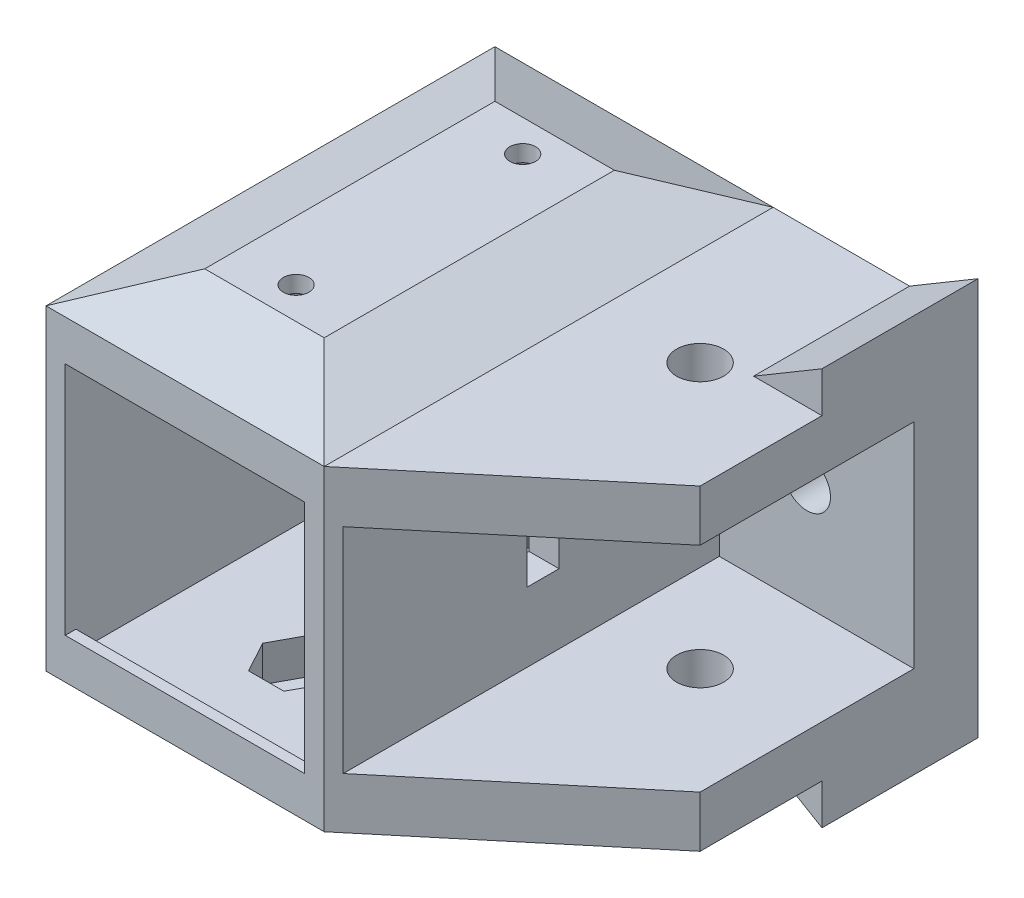
SolidWorks part; units mm, degrees
material "ABS"
ref_plane "Front Plane" through (0, 0, 0) normal (0, 0, 1) x (1, 0, 0)
ref_plane "Top Plane" through (0, 0, 0) normal (0, 1, 0) x (1, 0, 0)
ref_plane "Right Plane" through (0, 0, 0) normal (1, 0, 0) x (0, 0, -1)
sketch "Sketch1" plane through (0, 0, 0) normal (0, 0, 1) x (1, 0, 0)
  line L1 (2, 0) -> (45.2, 0)
  line L2 (0, 2) -> (0, 27.6)
  line L3 (2, 29.6) -> (45.2, 29.6)
  line L4 (45.2, 0) -> (45.2, 29.6)
  line L5 (2, 0) -> (0, 0)
  line L6 (-1.4495, 14.8) -> (46.6426, 14.8) construction
  line L7 (0, 0) -> (0, 2)
  line L8 (1.8, 27.7) -> (24.2, 27.7)
  line L9 (1.8, 27.7) -> (1.8, 1.9)
  line L10 (1.8, 1.9) -> (24.2, 1.9)
  line L11 (24.2, 27.7) -> (24.2, 1.9)
  line L12 (2, 29.6) -> (0, 29.6)
  line L13 (0, 29.6) -> (0, 27.6)
  circle A0 centre (35.2, 14.8) radius 2.2
  dimension "D10" = 10
  dimension "D2" = 11
  dimension "D3" = 14.8
  dimension "D4" = 1.8
  dimension "D7" = 22.4
  dimension "D8" = 25.8
  dimension "D9" = 1.9
extrude "Boss-Extrude1" add sketch "Sketch1" along normal blind 42
sketch "Sketch2" plane through (0, 29.6, 0) normal (0, 1, 0) x (1, 0, 0)
  line L0 (45.2, -26) -> (26.03, -42)
  line L1 (45.2, -42) -> (45.2, 0) construction
  line L2 (45.2, -42) -> (0, -42) construction
  line L3 (26.03, -42) -> (45.2, -42)
  line L4 (45.2, -42) -> (45.2, -26)
  dimension "D1" = 19.17
  dimension "D2" = 16
extrude "Cut-Extrude1" cut sketch "Sketch2" against normal through all
sketch "Sketch3" plane through (0, 0, 0) normal (0, 0, -1) x (-1, 0, 0)
  line L0 (-38.8, 0) -> (-45.2, -3.8)
  line L1 (0, 0) -> (-45.2, 0) construction
  line L2 (-45.2, -3.8) -> (-45.2, 0)
  line L3 (-45.2, 0) -> (-38.8, 0)
  line L4 (-46.2203, 14.8) -> (1.3358, 14.8) construction
  line L5 (-45.2, 29.6) -> (-38.8, 29.6)
  line L6 (-45.2, 33.4) -> (-45.2, 29.6)
  line L7 (-38.8, 29.6) -> (-45.2, 33.4)
  dimension "D1" = 6.4
  dimension "D2" = 3.8
extrude "Boss-Extrude2" add sketch "Sketch3" against normal blind 14.6
sketch "Sketch4" plane through (45.2, 0, 0) normal (1, 0, 0) x (0, 0, -1)
  line L0 (-42, 0) -> (-42, 29.6) construction
  line L1 (-6, 24.8) -> (-42, 24.8)
  line L2 (-6, 24.8) -> (-6, 4.8)
  line L3 (-6, 4.8) -> (-42, 4.8)
  line L4 (-42, 24.8) -> (-42, 4.8)
  line L5 (-26, 29.6) -> (-14.6, 29.6) construction
  line L6 (-26, 0) -> (-14.6, 0) construction
  line L7 (0, -3.8) -> (0, 33.4) construction
  dimension "D1" = 4.8
  dimension "D2" = 4.8
  dimension "D3" = 6
extrude "Cut-Extrude2" cut sketch "Sketch4" against normal blind 18.2
sketch "Sketch5" plane through (0, 29.6, 0) normal (0, 1, 0) x (1, 0, 0)
  line L0 (45.2, -26) -> (45.2, -14.6) construction
  line L1 (38.8, 0) -> (0, 0) construction
  circle A0 centre (35.2, -16) radius 2.2
  dimension "D1" = 10
  dimension "D2" = 16
extrude "Cut-Extrude3" cut sketch "Sketch5" against normal through all
sketch "Sketch16" plane through (0, 29.6, 0) normal (0, 1, 0) x (1, 0, 0)
  line L0 (26.03, -42) -> (26.03, 0)
  line L2 (26.03, 0) -> (0, 0)
  line L3 (0, 0) -> (0, -42)
  line L4 (0, -42) -> (26.03, -42)
  line L8 (0, -42) -> (0, 0) construction
extrude "Boss-Extrude6" add sketch "Sketch16" along normal blind 3
chamfer "Chamfer1" distance 3 angle 68 4 edges at (13.015, 32.6, 42) (26.03, 32.6, 21) (13.015, 32.6, 0) (0, 32.6, 21)
ref_plane "Plane1" through (0, 14.8, 0) normal (0, -1, 0) x (-1, 0, 0)
mirror "Mirror7" about plane through (0, 14.8, 0) normal (0, -1, 0) of "Boss-Extrude6", "Chamfer1"
sketch "Sketch6" plane through (0, 29.6, 0) normal (0, 1, 0) x (1, 0, 0)
  line L0 (11.35, -13.4) -> (9.7752, -10.5)
  line L1 (11.35, -13.4) -> (14.65, -13.4)
  line L3 (14.65, -13.4) -> (16.2442, -10.5)
  line L4 (14.65, -7.6) -> (16.2442, -10.5)
  line L5 (38.8, 0) -> (26.03, 0) construction
  line L6 (13, -2.324) -> (13, -15.7052) construction
  line L7 (11.35, -7.6) -> (9.7752, -10.5)
  line L8 (1.8, -42) -> (1.8, 0) construction
  line L9 (11.35, -7.6) -> (14.65, -7.6)
  line L13 (16.2442, -10.5) -> (9.7752, -10.5) construction
  dimension "D2" = 3.3
  dimension "D3" = 1.65
  dimension "D4" = 10.5
  dimension "D5" = 11.2
  dimension "D6" = 6.469
  dimension "D7" = 1.5942
  dimension "D11" = 2.9
extrude "Cut-Extrude4" cut sketch "Sketch6" along normal blind 3.35 from surface at -1.9 contours L7 L0 L1 L3 L4 L9 starting at face at (13, 27.7, 21)
sketch "Sketch10" plane through (0, 32.6, 0) normal (0, 1, 0) x (1, 0, 0)
  line L3 (13, -2.324) -> (13, -15.7052) construction
  line L4 (11.35, -7.6) -> (14.65, -7.6) construction
  circle A0 centre (13, -10.4) radius 1.2
  dimension "D1" = 2.8
extrude "Cut-Extrude10" cut sketch "Sketch10" against normal through all contours A0
mirror "Mirror4" about plane through (0, 14.8, 0) normal (0, -1, 0) of "Cut-Extrude4"
sketch "Sketch13" plane through (0, 0, 42) normal (0, 0, 1) x (1, 0, 0)
  line L0 (24.2, 1.9) -> (24.2, 27.7) construction
  line L1 (1.8, 1.9) -> (24.2, 1.9)
  line L2 (1.8, 1.9) -> (1.8, 3.8)
  line L3 (1.8, 3.8) -> (24.2, 3.8)
  line L4 (24.2, 1.9) -> (24.2, 3.8)
  line L6 (1.8, 27.7) -> (24.2, 27.7)
  line L7 (1.8, 27.7) -> (1.8, 25.8)
  line L8 (1.8, 25.8) -> (24.2, 25.8)
  line L9 (24.2, 27.7) -> (24.2, 25.8)
  dimension "D1" = 1.9
  dimension "D2" = 1.9
extrude "Boss-Extrude4" add sketch "Sketch13" against normal blind 1
sketch "Sketch14" plane through (27, 0, 0) normal (1, 0, 0) x (0, 0, -1)
  line L0 (-6, 24.8) -> (-41.1904, 24.8) construction
  line L1 (-8, 18.3) -> (-11, 18.3)
  line L2 (-8, 18.3) -> (-8, 11.3)
  line L3 (-8, 11.3) -> (-11, 11.3)
  line L4 (-11, 18.3) -> (-11, 11.3)
  line L5 (-21, 18.3) -> (-24, 18.3)
  line L6 (-21, 18.3) -> (-21, 11.3)
  line L7 (-21, 11.3) -> (-24, 11.3)
  line L8 (-24, 18.3) -> (-24, 11.3)
  line L9 (-42, 24.8) -> (-42, 4.8) construction
  dimension "D1" = 6.5
  dimension "D2" = 6.5
  dimension "D3" = 7
  dimension "D4" = 7
  dimension "D5" = 18
  dimension "D6" = 3
  dimension "D7" = 10
  dimension "D8" = 3
extrude "Cut-Extrude11" cut sketch "Sketch14" against normal up to surface (2.8 mm away) up to face at (24.2, 14.8, 31)
sketch "Sketch15" plane through (0, 0, 0) normal (0, 0, -1) x (-1, 0, 0)
  line L1 (-1.8, 1.9) -> (-24.2, 1.9)
  line L2 (-1.8, 1.9) -> (-1.8, 3.8)
  line L3 (-1.8, 3.8) -> (-24.2, 3.8)
  line L4 (-24.2, 1.9) -> (-24.2, 3.8)
  line L5 (-1.8, 27.7) -> (-24.2, 27.7)
  line L6 (-1.8, 27.7) -> (-1.8, 25.8)
  line L7 (-1.8, 25.8) -> (-24.2, 25.8)
  line L8 (-24.2, 27.7) -> (-24.2, 25.8)
extrude "Boss-Extrude5" add sketch "Sketch15" against normal blind 1
ref_plane "Plane2" through (0, 0, 21) normal (0, 0, 1) x (1, 0, 0)
mirror "Mirror5" about plane through (0, 0, 21) normal (0, 0, 1) of "Cut-Extrude10", "Cut-Extrude4", "Mirror4"
sketch "Sketch17" plane through (24.2, 0, 0) normal (-1, 0, 0) x (0, 0, 1)
  line L0 (24, 11.3) -> (21, 11.3) construction
  line L1 (24, 17.3) -> (37.2168, 17.3)
  line L2 (24, 17.3) -> (24, 12.3)
  line L3 (24, 12.3) -> (37.2168, 12.3)
  line L4 (37.2168, 17.3) -> (37.2168, 12.3)
  line L5 (30.6084, 12.3) -> (30.6084, 17.3) construction
  line L6 (24, 14.8) -> (37.2168, 14.8) construction
  line L8 (8, 17.3) -> (0, 17.3)
  line L9 (8, 17.3) -> (8, 12.3)
  line L10 (8, 12.3) -> (0, 12.3)
  line L11 (0, 17.3) -> (0, 12.3)
  line L12 (4, 12.3) -> (4, 17.3) construction
  line L13 (8, 14.8) -> (0, 14.8) construction
  line L15 (8, 11.3) -> (8, 18.3) construction
  line L16 (0, 3.8) -> (0, 25.8) construction
  point P92 (4, 14.8)
  point P156 (30.6084, 14.8)
  dimension "D1" = 5
  dimension "D2" = 13.2168
  dimension "D3" = 1
  dimension "D4" = 5
  dimension "D5" = 8
extrude "Boss-Extrude7" add sketch "Sketch17" along normal blind 3.2
fillet "Fillet1" radius 3 1 edges at (21, 14.8, 24)
fillet "Fillet2" radius 1 1 edges
fillet "Fillet3" radius 4 1 edges at (21, 14.8, 8)
